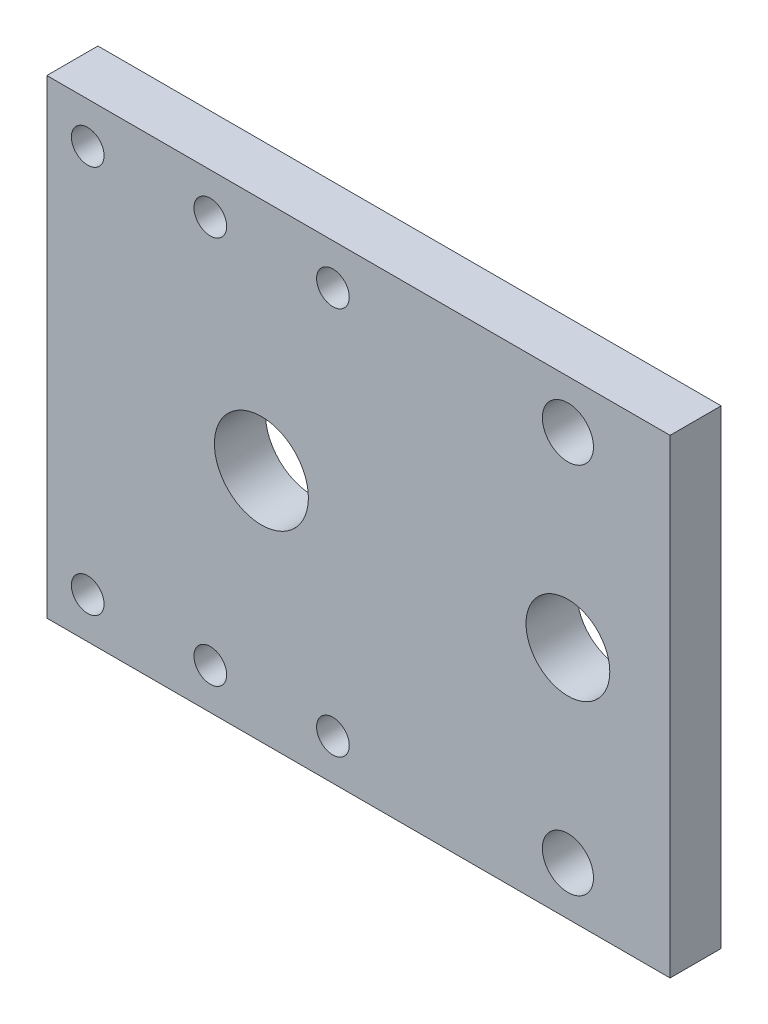
SolidWorks part; units mm, degrees
material "Acrylic (Medium-high impact)"
ref_plane "Front Plane" through (0, 0, 0) normal (0, 0, 1) x (1, 0, 0)
ref_plane "Top Plane" through (0, 0, 0) normal (0, 1, 0) x (1, 0, 0)
ref_plane "Right Plane" through (0, 0, 0) normal (1, 0, 0) x (0, 0, -1)
sketch "Sketch1" plane through (0, 0, 0) normal (0, 0, 1) x (1, 0, 0)
  line L0 (-25.3491, 0) -> (24.7222, 0) construction
  line L1 (40, -23) -> (-40, -23)
  line L2 (40, -23) -> (40, 23)
  line L3 (40, 23) -> (-40, 23)
  line L4 (-40, -23) -> (-40, 23)
  line L5 (40, -23) -> (-40, 23) construction
  line L6 (40, 23) -> (-40, -23) construction
  line L7 (30, 0) -> (30, 18.25)
  line L8 (-40, 23) -> (-25, 23)
  line L9 (-25, 23) -> (-25, -23)
  circle A0 centre (0, 0) radius 4.6
  circle A1 centre (30, 0) radius 4.1
  circle A2 centre (30, 18.25) radius 2.5
  circle A3 centre (30, -18.25) radius 2.5
  point P0 (0, 0)
  dimension "D1" = 9.2
  dimension "D2" = 8.2
  dimension "D7" = 5
  dimension "D3" = 46
  dimension "D4" = 30
  dimension "D5" = 80
  dimension "D6" = 18.25
  dimension "D8" = 15
extrude "Boss-Extrude1" add sketch "Sketch1" along normal blind 5 contours L4 L1 L2 L3 A0 A2 A1 A3 region at (6.9444, 0, 0)
sketch "Sketch2" plane through (0, 0, 5) normal (0, 0, 1) x (1, 0, 0)
  line L0 (-25, -23) -> (-25, 23)
  line L1 (-25, -23) -> (-5, -23)
  line L2 (-25, 23) -> (-5, 23)
  line L3 (-5, -23) -> (-5, 23)
  line L4 (-25, 23) -> (-25, -23)
  line L5 (-25, -23) -> (40, -23)
  line L6 (40, -23) -> (40, 23)
  line L7 (40, 23) -> (-25, 23)
  line L9 (-25, -23) -> (40, -23)
  line L10 (40, -23) -> (40, 23)
  line L11 (40, 23) -> (-25, 23)
  line L12 (-17, 19) -> (-25, 19)
  line L13 (-17, 19) -> (-5, 19)
  line L14 (-5, 19) -> (7, 19)
  line L16 (-5, 0) -> (-25, 0)
  line L20 (-25, 23) -> (-25, -23)
  circle A0 centre (-17, 19) radius 1.6
  circle A1 centre (-5, 19) radius 1.6
  circle A5 centre (7, 19) radius 1.6
  circle A6 centre (7, -19) radius 1.6
  circle A7 centre (-5, -19) radius 1.6
  circle A8 centre (-17, -19) radius 1.6
  point P4 (0, 0)
  point P8 (0, 0)
  point P20 (0, 0)
  point P24 (0, 0)
  dimension "D5" = 3.2
  dimension "D6" = 3.2
  dimension "D7" = 19
  dimension "D8" = 3.2
  dimension "D2" = 20
  dimension "D3" = 12
  dimension "D4" = 12
  dimension "D9" = 8
  dimension "D1" = 0
extrude "Cut-Extrude1" cut sketch "Sketch2" against normal blind 10 contours A8 | A7 L3 | A7 L3 | A6 | A5 | L14 A1 L3 | L3 A1 L13 | L13 A1 L3 | L3 A1 L14 | L13 A0 L12 | L12 A0 L13 region at (7, 20.5547, 5) region at (-5.6791, -19, 5) region at (-4.3209, -19, 5) region at (-17, 19.6791, 5) region at (-17, 18.3209, 5) region at (-5.6791, 18.3209, 5) region at (-4.3209, 18.3209, 5) region at (-5.6791, 19.6791, 5) region at (-4.3209, 19.6791, 5) region at (7, -19, 5) region at (-17, -19, 5)
sketch "Sketch3" plane through (0, 0, 5) normal (0, 0, 1) x (1, 0, 0)
  line L0 (-25, 23) -> (-21, 23)
  line L1 (-21, 23) -> (-21, -23)
  line L4 (40, 23) -> (-25, 23)
  line L5 (-25, 23) -> (-25, -23)
  line L6 (-25, -23) -> (40, -23)
  line L7 (40, -23) -> (40, 23)
  line L8 (40, 23) -> (-25, 23)
  line L9 (-25, 23) -> (-25, -23)
  line L10 (-25, -23) -> (40, -23)
  line L11 (40, -23) -> (40, 23)
  line M10 (40, 23) -> (-25, 23)
  line M11 (-25, 23) -> (-25, -23)
  line M12 (-25, -23) -> (40, -23)
  dimension "D2" = 4
  dimension "D1" = 0
extrude "Cut-Extrude2" cut sketch "Sketch3" against normal through all contours L1 M10 M11 M12 region at (-23, 0, 5)
